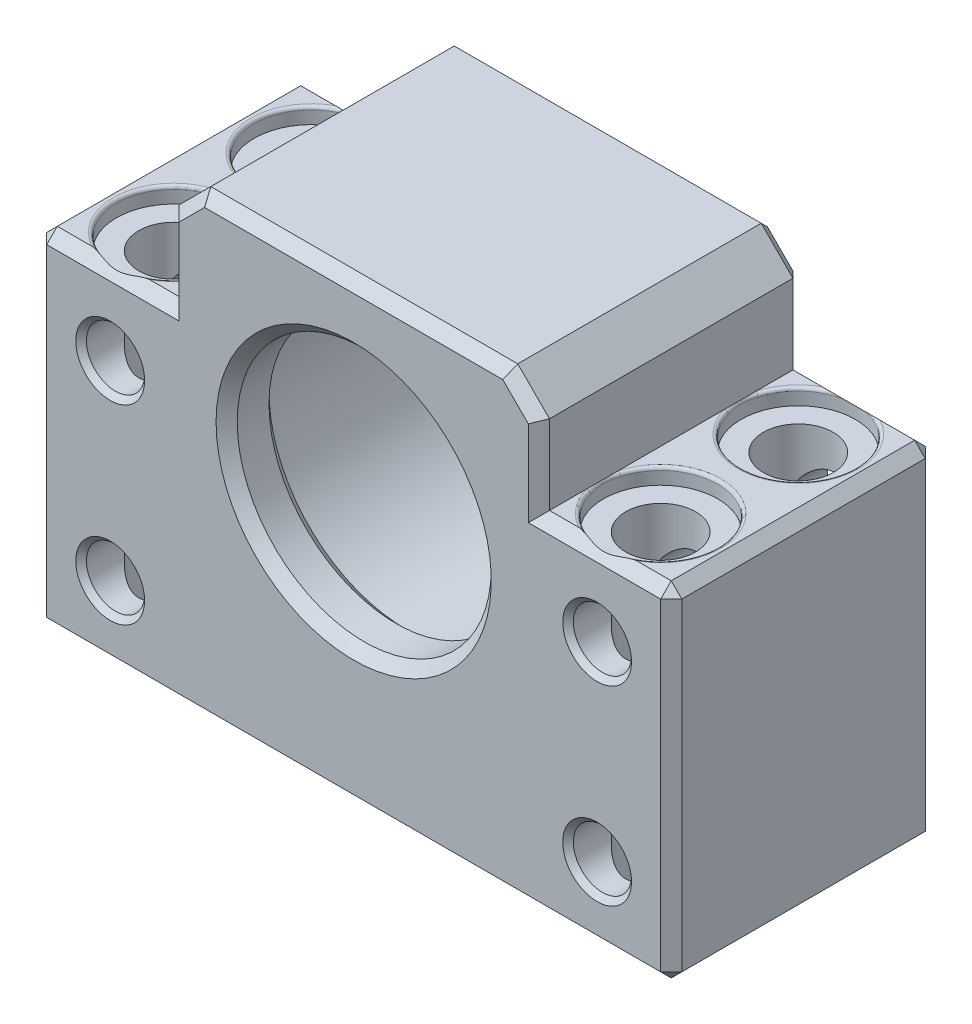
SolidWorks part; units mm, degrees
material "1060 Alloy"
ref_plane "Front Plane" through (0, 0, 0) normal (0, 0, 1) x (1, 0, 0)
ref_plane "Top Plane" through (0, 0, 0) normal (0, 1, 0) x (1, 0, 0)
ref_plane "Right Plane" through (0, 0, 0) normal (1, 0, 0) x (0, 0, -1)
sketch "Sketch1" plane through (0, 0, 0) normal (0, 0, 1) x (1, 0, 0)
  line L0 (-17.5, 0) -> (-17.5, -43) construction
  line L1 (0, 0) -> (-30, 0) construction
  line L2 (0, 0) -> (0, -43) construction
  line L3 (0, -43) -> (-30, -43) construction
  line L4 (-30, 0) -> (-30, -43) construction
  line L5 (-30, -10.5) -> (0, -10.5) construction
  line L6 (17.5, 0) -> (-17.5, 0)
  line L7 (-17.5, 0) -> (-17.5, -10.5)
  line L8 (-17.5, -10.5) -> (-30, -10.5)
  line L9 (-30, -10.5) -> (-30, -43)
  line L10 (-30, -43) -> (30, -43)
  line L11 (30, -10.5) -> (30, -43)
  line L12 (17.5, -10.5) -> (30, -10.5)
  line L13 (17.5, 0) -> (17.5, -10.5)
  circle A0 centre (0, -18) radius 12 construction
  circle A1 centre (0, -18) radius 12
  dimension "D5" = 24
  dimension "D1" = 30
  dimension "D2" = 43
  dimension "D3" = 17.5
  dimension "D4" = 32.5
  dimension "D6" = 25
extrude "Boss-Extrude1" add sketch "Sketch1" along normal blind 25
chamfer "Chamfer2" distance 3 angle 45 2 edges at (-17.5, 0, 12.5) (17.5, 0, 12.5)
chamfer "Chamfer1" distance 1 angle 45 24 edges at (0, -43, 25) (23.75, -10.5, 0) (17.5, -6.75, 0) (30, -43, 12.5) (30, -26.75, 0) (30, -26.75, 25) (30, -10.5, 12.5) (23.75, -10.5, 25) (17.5, -6.75, 25) (0, 0, 25) (-23.75, -10.5, 0) (0, -43, 0) (-17.5, -6.75, 0) (-30, -26.75, 0) (-30, -43, 12.5) (-30, -10.5, 12.5) (-17.5, -6.75, 25) (-23.75, -10.5, 25) (-30, -26.75, 25) (0, 0, 0) (-16, -1.5, 25) (-16, -1.5, 0) (16, -1.5, 0) (16, -1.5, 25)
sketch "Sketch2" plane through (0, 0, 0) normal (0, 0, 1) x (1, 0, 0)
  line L0 (0, 0) -> (0, -43) construction
  line L1 (29, -43) -> (-29, -43) construction
  circle A0 centre (0, -18) radius 14
  dimension "D1" = 28
  dimension "D2" = 25
extrude "Cut-Extrude1" cut sketch "Sketch2" along normal blind 20
chamfer "Chamfer3" distance 1 angle 45 3 edges at (12, -18, 20) (12, -18, 25) (14, -18, 0)
sketch "Sketch3" plane through (0, 0, 0) normal (0, 0, -1) x (-1, 0, 0)
  line L0 (0, 0) -> (0, -43) construction
  line L1 (29, -43) -> (-29, -43) construction
  line L2 (-11.85, -18) -> (11.85, -18) construction
  line L3 (-11.85, -6.15) -> (11.85, -6.15) construction
  line L4 (-11.85, -6.15) -> (-11.85, -29.85) construction
  line L5 (-11.85, -29.85) -> (11.85, -29.85) construction
  line L6 (11.85, -6.15) -> (11.85, -29.85) construction
  line L7 (-11.85, -6.15) -> (11.85, -29.85) construction
  line L8 (-11.85, -29.85) -> (11.85, -6.15) construction
  circle A0 centre (-11.85, -6.15) radius 1.5
  circle A1 centre (11.85, -6.15) radius 1.5
  circle A2 centre (11.85, -29.85) radius 1.5
  circle A3 centre (-11.85, -29.85) radius 1.5
  point P5 (0, -18)
  dimension "D2" = 3
  dimension "D1" = 25
  dimension "D3" = 23.7
extrude "Cut-Extrude2" cut sketch "Sketch3" against normal blind 12
chamfer "Chamfer4" distance 0.1 angle 45 4 edges at (13.35, -29.85, 0) (-13.35, -29.85, 0) (-10.35, -6.15, 0) (10.35, -6.15, 0)
sketch "Sketch4" plane through (0, 0, 0) normal (0, 0, -1) x (-1, 0, 0)
  line L0 (0, 0) -> (0, -43) construction
  line L1 (29, -43) -> (-29, -43) construction
  line L2 (-23, -27) -> (23, -27) construction
  line L3 (-23, -18) -> (23, -18) construction
  line L4 (-23, -18) -> (-23, -36) construction
  line L5 (-23, -36) -> (23, -36) construction
  line L6 (23, -18) -> (23, -36) construction
  line L7 (-23, -18) -> (23, -36) construction
  line L8 (-23, -36) -> (23, -18) construction
  circle A0 centre (-23, -18) radius 2.75
  circle A1 centre (23, -18) radius 2.75
  circle A2 centre (23, -36) radius 2.75
  circle A3 centre (-23, -36) radius 2.75
  point P5 (0, -27)
  dimension "D1" = 5.5
  dimension "D2" = 46
  dimension "D3" = 18
  dimension "D4" = 16
extrude "Cut-Extrude3" cut sketch "Sketch4" against normal through all
sketch "Sketch5" plane through (0, -43, 0) normal (0, -1, 0) x (1, 0, 0)
  line L0 (0, 25) -> (0, 0) construction
  line L1 (-29, 25) -> (29, 25) construction
  line L2 (-23, 12.5) -> (23, 12.5) construction
  line L3 (-23, 19) -> (23, 19) construction
  line L4 (-23, 19) -> (-23, 6) construction
  line L5 (-23, 6) -> (23, 6) construction
  line L6 (23, 19) -> (23, 6) construction
  line L7 (-23, 19) -> (23, 6) construction
  line L8 (-23, 6) -> (23, 19) construction
  circle A0 centre (-23, 19) radius 3.3
  circle A1 centre (23, 19) radius 3.3
  circle A2 centre (23, 6) radius 3.3
  circle A3 centre (-23, 6) radius 3.3
  point P5 (0, 12.5)
  dimension "D1" = 6.6
  dimension "D2" = 46
  dimension "D3" = 13
extrude "Cut-Extrude4" cut sketch "Sketch5" against normal up to next
chamfer "Chamfer5" distance 0.5 angle 45 12 edges at (-20.25, -18, 0) (-25.75, -36, 0) (25.75, -36, 0) (20.25, -18, 0) (-25.75, -36, 25) (25.75, -36, 25) (20.25, -18, 25) (-20.25, -18, 25) (23, -43, 2.7) (23, -43, 22.3) (-23, -43, 9.3) (-23, -43, 15.7)
sketch "Sketch6" plane through (0, -10.5, 0) normal (0, 1, 0) x (1, 0, 0)
  line L0 (0, 0) -> (0, -25) construction
  line L1 (14.0858, -25) -> (-14.0858, -25) construction
  line L2 (-23, -12.5) -> (23, -12.5) construction
  line L3 (-23, -6) -> (23, -6) construction
  line L4 (-23, -6) -> (-23, -19) construction
  line L5 (-23, -19) -> (23, -19) construction
  line L6 (23, -6) -> (23, -19) construction
  line L7 (-23, -6) -> (23, -19) construction
  line L8 (-23, -19) -> (23, -6) construction
  circle A0 centre (-23, -6) radius 5.4
  circle A1 centre (23, -6) radius 5.4
  circle A2 centre (23, -19) radius 5.4
  circle A3 centre (-23, -19) radius 5.4
  point P5 (0, -12.5)
  dimension "D3" = 10.8
  dimension "D1" = 46
  dimension "D2" = 13
extrude "Cut-Extrude5" cut sketch "Sketch6" against normal blind 1.5
fillet "Fillet1" radius 0.3 4 edges at (-23, -10.5, 13.6) (23, -10.5, 13.6) (-23, -10.5, 11.4) (23, -10.5, 11.4)
